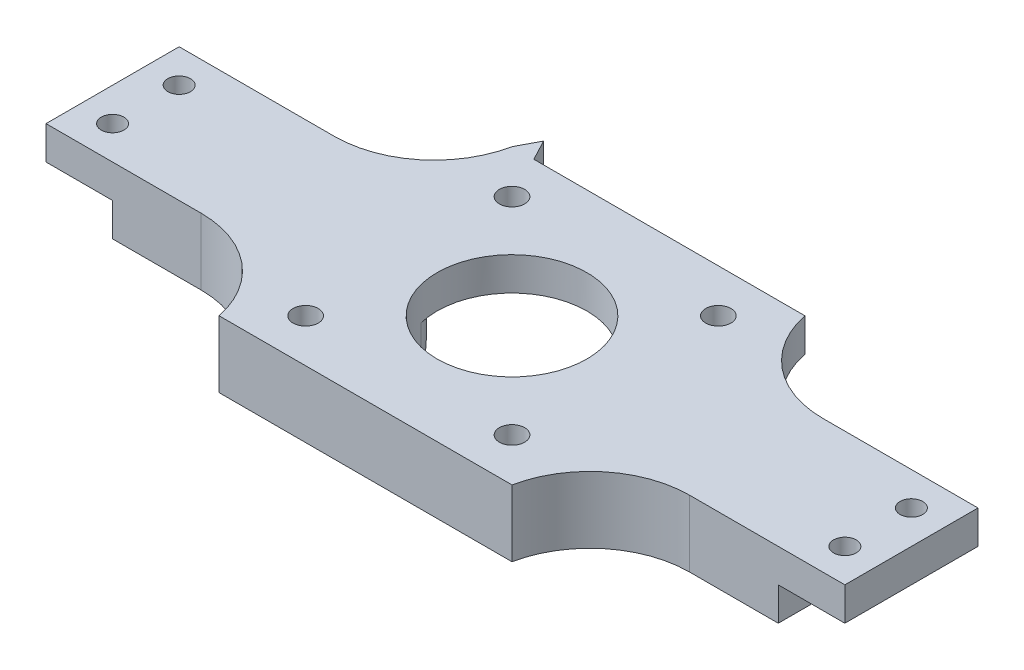
SolidWorks part; units mm, degrees
ref_plane "Ebene vorne" through (0, 0, 0) normal (0, 0, 1) x (1, 0, 0)
ref_plane "Ebene oben" through (0, 0, 0) normal (0, 1, 0) x (1, 0, 0)
ref_plane "Ebene rechts" through (0, 0, 0) normal (1, 0, 0) x (0, 0, -1)
sketch "Skizze1" plane through (0, 0, 0) normal (0, 1, 0) x (1, 0, 0)
  line L0 (-60, -4.8) -> (-22, -4.8)
  line L1 (60, -4.8) -> (60, 15.2)
  line L2 (60, 15.2) -> (22, 15.2)
  line L3 (0, 10.4) -> (0, 0) construction
  line L4 (-60, -4.8) -> (-60, 15.2)
  line L5 (22, -4.8) -> (60, -4.8)
  line L6 (-22, 15.2) -> (-22, 27.2)
  line L7 (-15.5, -10.3) -> (15.5, -10.3) construction
  line L8 (-15.5, -10.3) -> (-15.5, 20.7) construction
  line L9 (-15.5, 20.7) -> (15.5, 20.7) construction
  line L10 (15.5, -10.3) -> (15.5, 20.7) construction
  line L11 (-15.5, -10.3) -> (15.5, 20.7) construction
  line L12 (-15.5, 20.7) -> (15.5, -10.3) construction
  line L13 (-22, -16.8) -> (22, -16.8)
  line L14 (-22, -16.8) -> (-22, -4.8)
  line L15 (-22, 27.2) -> (0, 27.2)
  line L16 (22, -16.8) -> (22, -4.8)
  line L17 (-22, -16.8) -> (22, 27.2) construction
  line L18 (-22, 27.2) -> (22, -16.8) construction
  line L19 (22, 15.2) -> (22, 27.2)
  line L20 (-22, 15.2) -> (-60, 15.2)
  line L21 (0, 5.2) -> (-66.3854, 5.2) construction
  line L22 (0, 5.2) -> (0, 50.559) construction
  line L23 (0, 27.2) -> (22, 27.2)
  point P7 (0, 5.2)
  point P8 (0, 5.2)
  point P11 (-60, 5.2)
  dimension "D3" = 31
  dimension "D1" = 120
  dimension "D2" = 20
  dimension "D4" = 44
  dimension "D5" = 44
extrude "Aufsatz-Linear austragen1" add sketch "Skizze1" along normal blind 10
sketch "Skizze4" plane through (-60, 0, 0) normal (1, 0, 0) x (0, 0, -1)
  line L0 (-4.8, 10) -> (15.2, 10)
  line L1 (15.2, 10) -> (15.2, 9.0736)
  line L2 (15.2, 10) -> (15.2, 0) construction
  line L3 (-4.8, 10) -> (-4.8, 5.2708)
  line L4 (-4.8, 10) -> (-4.8, 0) construction
  arc A1 (-4.8, 5.2708) -> (15.2, 9.0736) centre (58.0172, -270.6068) cw
extrude "Schnitt-Linear austragen2" [suppressed] cut sketch "Skizze4" along normal blind 10
fillet "Verrundung1" [suppressed] radius 10
mirror "Spiegeln1" [suppressed] about plane through (0, 0, 0) normal (1, 0, 0)
sketch "Skizze6" plane through (0, 10, 0) normal (0, 1, 0) x (1, 0, 0)
  line L0 (0, 27.2) -> (0, -16.8) construction
  line L3 (22, 27.2) -> (-22, 27.2) construction
  line L4 (-15.5, -10.3) -> (15.5, -10.3) construction
  line L5 (-15.5, -10.3) -> (-15.5, 20.7) construction
  line L6 (-15.5, 20.7) -> (15.5, 20.7) construction
  line L7 (15.5, -10.3) -> (15.5, 20.7) construction
  line L8 (-15.5, -10.3) -> (15.5, 20.7) construction
  line L9 (-15.5, 20.7) -> (15.5, -10.3) construction
  line L10 (-22, -16.8) -> (22, -16.8) construction
  circle A0 centre (15.5, 20.7) radius 1.9
  circle A1 centre (15.5, -10.3) radius 1.9
  circle A2 centre (-15.5, -10.3) radius 1.9
  circle A3 centre (-15.5, 20.7) radius 1.9
  circle A4 centre (0, 5.2) radius 11.25
  point P6 (0, 5.2)
  dimension "D2" = 3.8
  dimension "D3" = 22.5
  dimension "D1" = 31
extrude "Schnitt-Linear austragen4" cut sketch "Skizze6" against normal through all
sketch "Skizze7" plane through (-22, 0, 0) normal (-1, 0, 0) x (0, 0, 1)
  line L0 (-36.0808, 5) -> (-15.2, 5)
  line L2 (-15.2, 10) -> (-15.2, 0) construction
  line L3 (-15.2, 5) -> (-15.2, 0)
  line L4 (-15.2, 0) -> (-36.0808, 0)
  line L6 (-36.0808, 5) -> (-36.0808, 0)
extrude "Schnitt-Linear austragen5" cut sketch "Skizze7" against normal through all
fillet "Verrundung2" [suppressed] radius 10
fillet "Verrundung3" radius 15 4 edges at (-22, 7.5, -15.2) (-22, 5, 4.8) (22, 5, 4.8) (22, 7.5, -15.2)
fillet "Verrundung4" radius 17 2 edges at (-5.1539, 2.5, -15.2) (5.1539, 2.5, -15.2) conic radius 60
sketch "Skizze8" plane through (0, 0, -15.2) normal (0, 0, -1) x (-1, 0, 0)
  line L6 (-60, 5) -> (-50, 5)
  line L7 (-60, 10) -> (-60, 0) construction
  line L8 (-50, 5) -> (-50, 0)
  line L9 (-60, 0) -> (-27.369, 0) construction
  line L10 (-50, 0) -> (-60, 0)
  line L11 (-60, 0) -> (-60, 5)
  line L12 (0, 0) -> (0, 15.1362) construction
  line L13 (-10.8992, 0) -> (10.8992, 0) construction
  line L14 (60, 0) -> (60, 5)
  line L15 (50, 0) -> (60, 0)
  line L16 (50, 5) -> (50, 0)
  line L17 (60, 5) -> (50, 5)
  dimension "D1" = 10
extrude "Schnitt-Linear austragen6" cut sketch "Skizze8" against normal through all and the other way through all
sketch "Skizze9" plane through (0, 5, 0) normal (0, -1, 0) x (1, 0, 0)
  line L0 (-60, -5.2) -> (-50, -5.2) construction
  line L1 (-60, 4.8) -> (-60, -15.2) construction
  line L2 (-50, 4.8) -> (-50, -15.2) construction
  line L3 (-55, -5.2) -> (-55, 4.8) construction
  line L4 (-60, 4.8) -> (-50, 4.8) construction
  line L5 (0, 0) -> (0, -8.3592) construction
  circle A0 centre (-55, -0.2) radius 1.7
  circle A1 centre (-55, -10.2) radius 1.7
  circle A2 centre (55, -10.2) radius 1.7
  circle A3 centre (55, -0.2) radius 1.7
  dimension "D1" = 3.4
extrude "Schnitt-Linear austragen7" cut sketch "Skizze9" against normal blind 10
sketch "Skizze10" plane through (0, 10, 0) normal (0, 1, 0) x (1, 0, 0)
  line L0 (-22, 27.2) -> (-20.3604, 30.3072)
  line L1 (-20.3604, 30.3072) -> (-20.3604, 27.2) construction
  line L2 (22, 27.2) -> (-22, 27.2) construction
  line L3 (-18.7207, 27.2) -> (-20.3604, 30.3072)
  line L4 (-18.7207, 27.2) -> (-22, 27.2)
extrude "Aufsatz-Linear austragen2" add sketch "Skizze10" against normal blind 5
